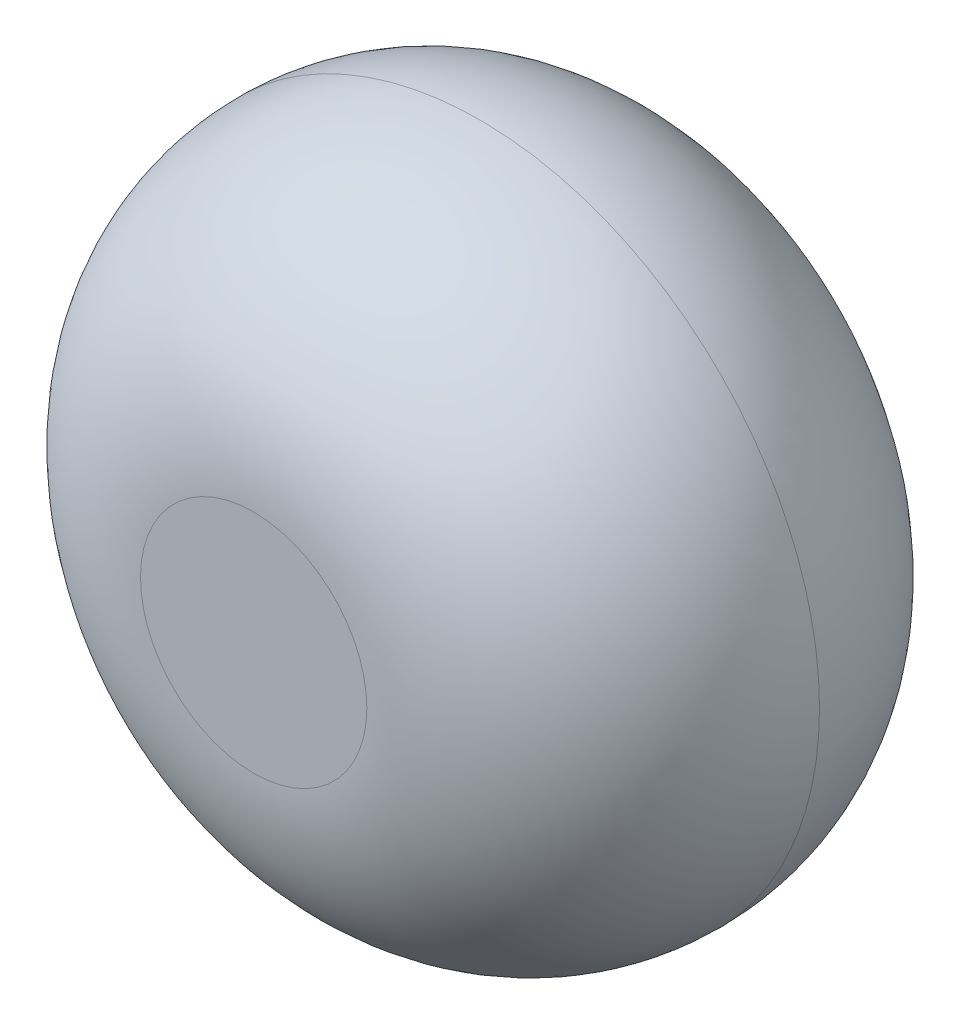
SolidWorks part; units mm, degrees
ref_plane "Plan de face" through (0, 0, 0) normal (0, 0, 1) x (1, 0, 0)
ref_plane "Plan de dessus" through (0, 0, 0) normal (0, 1, 0) x (1, 0, 0)
ref_plane "Plan de droite" through (0, 0, 0) normal (1, 0, 0) x (0, 0, -1)
sketch "Esquisse1" plane through (0, 0, 0) normal (0, 0, 1) x (1, 0, 0)
  circle A0 centre (0, 0) radius 38.1
  dimension "D1" = 76.2
extrude "Boss.-Extru.1" add sketch "Esquisse1" along normal blind 50.8
fillet "Congé1" radius 25.4 2 edges at (38.1, 0, 0) (38.1, 0, 50.8)
